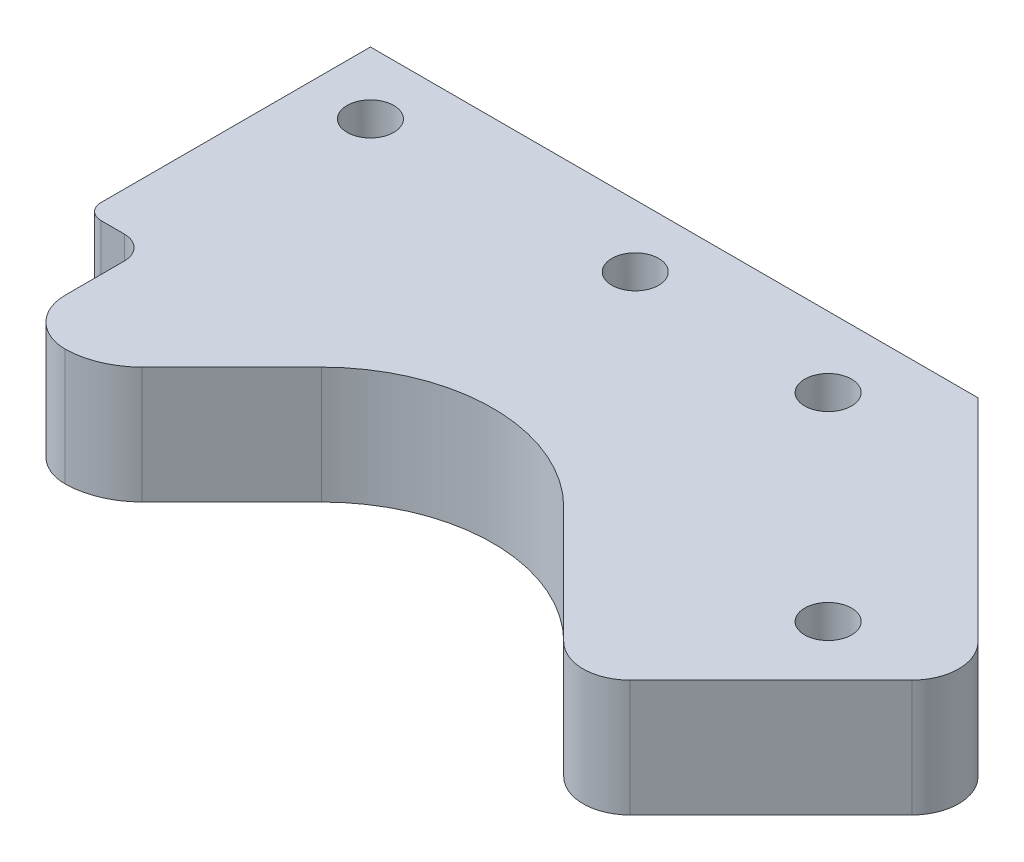
SolidWorks part; units mm, degrees
ref_plane "Front Plane" through (0, 0, 0) normal (0, 0, 1) x (1, 0, 0)
ref_plane "Top Plane" through (0, 0, 0) normal (0, 1, 0) x (1, 0, 0)
ref_plane "Right Plane" through (0, 0, 0) normal (1, 0, 0) x (0, 0, -1)
sketch "Sketch3" plane through (0, 5.4967, 0) normal (0, -1, 0) x (1, 0, 0)
  line L8 (-43.5722, -214.6789) -> (-43.5722, 19.4919) construction
  line L9 (-58.5723, 18.9356) -> (-63.5723, 18.9356)
  line L12 (-35.7941, 11.7137) -> (-26.1725, 21.3353)
  line L13 (-58.5723, 18.9356) -> (-51.3504, 11.7137)
  line L14 (-26.1725, 21.3353) -> (-12.8767, 8.0395)
  line L16 (-28.5722, -7.6561) -> (-12.8767, 8.0395)
  line L17 (-58.5723, -7.6561) -> (-28.5722, -7.6561)
  line L18 (-63.5723, 18.9356) -> (-63.5723, 5.6398)
  line L19 (-43.5722, 19.4919) -> (-32.5722, 19.4919) construction
  line L20 (-58.5723, -7.6561) -> (-63.5723, 5.6398)
  circle A0 centre (-43.5722, 19.4919) radius 11 construction
  arc A2 (-51.3504, 11.7137) -> (-35.7941, 11.7137) centre (-43.5722, 19.4919) ccw
  circle A4 centre (-33.6728, -3.1355) radius 1.5
  circle A5 centre (-20.9448, 9.5924) radius 1.5
extrude "Boss-Extrude1" add sketch "Sketch3" along normal blind 8
sketch "Sketch4" plane through (0, 25.4967, 0) normal (0, 1, 0) x (1, 0, 0)
  line L0 (-67.5734, 21.5545) -> (-67.5734, -11.9295) construction
  line L3 (-65.0723, -10.6398) -> (-67.5734, -10.6398)
  line L4 (-67.5734, 7.6561) -> (-67.5734, -10.6398)
  line L5 (-63.5723, -5.6398) -> (-63.5723, -18.9356)
  line L6 (-63.5723, -12.1398) -> (-63.5723, -18.9356)
  line L10 (-26.1725, -21.3353) -> (-12.8767, -8.0395)
  line L11 (-28.5722, 7.6561) -> (-58.5723, 7.6561)
  line L19 (-28.5722, 7.6561) -> (-67.5734, 7.6561)
  line L21 (-26.1725, -21.3353) -> (-12.8767, -8.0395)
  line L22 (-12.8767, -8.0395) -> (-28.5722, 7.6561)
  line L23 (-12.8767, -8.0395) -> (-28.5722, 7.6561)
  line L26 (-58.5723, 7.6561) -> (-63.5723, -5.6398)
  line L27 (-63.5723, -18.9356) -> (-58.5723, -18.9356)
  line L28 (-63.5723, -18.9356) -> (-58.5723, -18.9356)
  line L29 (-58.5723, -18.9356) -> (-51.3504, -11.7137)
  line L30 (-58.5723, -18.9356) -> (-51.3504, -11.7137)
  line L31 (-35.7941, -11.7137) -> (-26.1725, -21.3353)
  line L32 (-35.7941, -11.7137) -> (-26.1725, -21.3353)
  arc A1 (-35.7941, -11.7137) -> (-51.3504, -11.7137) centre (-43.5722, -19.4919) ccw
  arc A2 (-35.7941, -11.7137) -> (-51.3504, -11.7137) centre (-43.5722, -19.4919) ccw
  arc A3 (-63.5723, -12.1398) -> (-65.0723, -10.6398) centre (-65.0723, -12.1398) ccw
  dimension "D3" = 1.5
  dimension "D1" = 0
extrude "Boss-Extrude2" add sketch "Sketch4" along normal blind 8 separate body
sketch "Sketch9" plane through (0, 25.4967, 0) normal (0, -1, 0) x (1, 0, 0)
  line L0 (-34.7096, -7.6561) -> (-42.7096, 0.3439)
  line L2 (-42.7096, 0.3439) -> (-58.4567, 0.3439)
  line L3 (-34.7096, -7.6561) -> (-58.4567, -7.6561)
  line L4 (-58.4567, -7.6561) -> (-58.4567, 0.3439)
  line L6 (-58.5723, -7.6561) -> (-28.5722, -7.6561) construction
  line L7 (-20.9448, 9.5924) -> (-33.6728, -3.1355) construction
  dimension "D1" = 8
extrude "Boss-Extrude3" add sketch "Sketch9" along normal up to surface (20 mm away) up to face at (-44.3395, 5.4967, 8.6421)
sketch "Sketch10" plane through (0, 0, -7.6561) normal (0, 0, -1) x (-1, 0, 0)
  circle A0 centre (43.5723, 15.4967) radius 5
  circle A1 centre (43.5723, 15.4967) radius 7.5
extrude "Boss-Extrude4" add sketch "Sketch10" along normal blind 10
fillet "Fillet1" radius 3 6 edges at (-26.1725, 29.4967, 21.3353) (-12.8767, 29.4967, 8.0395) (-26.1725, 1.4967, 21.3353) (-12.8767, 1.4967, 8.0395) (-63.5723, 29.4967, 18.9356) (-63.5723, 1.4967, 18.9356)
sketch "Sketch11" plane through (0, 25.4967, 0) normal (0, -1, 0) x (1, 0, 0)
  line L12 (-58.5723, 18.9356) -> (-60.5723, 18.9356)
  line L13 (-63.5723, 15.9356) -> (-63.5723, 12.1398)
  line L15 (-67.5734, -7.6561) -> (-58.4567, -7.6561)
  line L16 (-58.4567, -7.6561) -> (-58.4567, 0.3439)
  line L17 (-58.4567, 0.3439) -> (-42.7096, 0.3439)
  line L18 (-42.7096, 0.3439) -> (-34.7096, -7.6561)
  line L19 (-34.7096, -7.6561) -> (-28.5722, -7.6561)
  line L20 (-28.5722, -7.6561) -> (-14.998, 5.9181)
  line L21 (-14.998, 10.1608) -> (-24.0512, 19.214)
  line L22 (-28.2939, 19.214) -> (-35.7941, 11.7137)
  line L23 (-51.3504, 11.7137) -> (-58.5723, 18.9356)
  line L24 (-58.5723, 18.9356) -> (-60.5723, 18.9356)
  line L25 (-63.5723, 15.9356) -> (-63.5723, 12.1398)
  line L27 (-67.5734, -7.6561) -> (-58.4567, -7.6561)
  line L28 (-58.4567, -7.6561) -> (-58.4567, 0.3439)
  line L29 (-58.4567, 0.3439) -> (-42.7096, 0.3439)
  line L30 (-42.7096, 0.3439) -> (-34.7096, -7.6561)
  line L31 (-34.7096, -7.6561) -> (-28.5722, -7.6561)
  line L32 (-28.5722, -7.6561) -> (-14.998, 5.9181)
  line L33 (-14.998, 10.1608) -> (-24.0512, 19.214)
  line L34 (-28.2939, 19.214) -> (-35.7941, 11.7137)
  line L35 (-51.3504, 11.7137) -> (-58.5723, 18.9356)
  line L39 (-65.0723, 10.6398) -> (-67.5734, 10.6398)
  line L40 (-65.0723, 10.6398) -> (-67.5734, 10.6398)
  line L41 (-67.5734, 10.6398) -> (-67.5734, -7.6561)
  line L42 (-67.5734, 10.6398) -> (-67.5734, -7.6561)
  arc A4 (-60.5723, 18.9356) -> (-63.5723, 15.9356) centre (-60.5723, 15.9356) ccw
  arc A5 (-14.998, 5.9181) -> (-14.998, 10.1608) centre (-17.1193, 8.0395) ccw
  arc A6 (-24.0512, 19.214) -> (-28.2939, 19.214) centre (-26.1725, 17.0926) ccw
  arc A7 (-51.3504, 11.7137) -> (-35.7941, 11.7137) centre (-43.5722, 19.4919) ccw
  arc A8 (-60.5723, 18.9356) -> (-63.5723, 15.9356) centre (-60.5723, 15.9356) ccw
  arc A9 (-14.998, 5.9181) -> (-14.998, 10.1608) centre (-17.1193, 8.0395) ccw
  arc A10 (-24.0512, 19.214) -> (-28.2939, 19.214) centre (-26.1725, 17.0926) ccw
  arc A11 (-51.3504, 11.7137) -> (-35.7941, 11.7137) centre (-43.5722, 19.4919) ccw
  arc A14 (-65.0723, 10.6398) -> (-63.5723, 12.1398) centre (-65.0723, 12.1398) ccw
  arc A15 (-65.0723, 10.6398) -> (-63.5723, 12.1398) centre (-65.0723, 12.1398) ccw
  dimension "D1" = 0
extrude "Cut-Extrude1" cut sketch "Sketch11" against normal blind 0.5
sketch "Sketch12" plane through (0, 5.4967, 0) normal (0, 1, 0) x (1, 0, 0)
  line L0 (-67.5734, -10.6398) -> (-65.0723, -10.6398) construction
  line L1 (-67.5734, 7.6561) -> (-67.5734, -10.6398) construction
  line L3 (-67.5734, -10.6398) -> (-65.0723, -10.6398)
  line L4 (-67.5734, 7.6561) -> (-67.5734, -10.6398)
  line L5 (-65.6492, -5.6398) -> (-67.5734, 7.6561)
  line L12 (-63.5723, -5.6398) -> (-63.5723, -15.9356)
  line L13 (-60.5723, -18.9356) -> (-58.5723, -18.9356)
  line L14 (-58.5723, -18.9356) -> (-51.3504, -11.7137)
  line L15 (-35.7941, -11.7137) -> (-28.2939, -19.214)
  line L16 (-24.0512, -19.214) -> (-14.998, -10.1608)
  line L17 (-14.998, -5.9181) -> (-28.5722, 7.6561)
  line L18 (-28.5722, 7.6561) -> (-34.7096, 7.6561)
  line L19 (-34.7096, 7.6561) -> (-42.7096, -0.3439)
  line L20 (-42.7096, -0.3439) -> (-58.4567, -0.3439)
  line L21 (-58.4567, -0.3439) -> (-58.4567, 7.6561)
  line L22 (-58.4567, 7.6561) -> (-58.5723, 7.6561)
  line L23 (-58.5723, 7.6561) -> (-63.5723, -5.6398)
  line L24 (-63.5723, -12.1398) -> (-63.5723, -15.9356)
  line L25 (-60.5723, -18.9356) -> (-58.5723, -18.9356)
  line L26 (-58.5723, -18.9356) -> (-51.3504, -11.7137)
  line L27 (-35.7941, -11.7137) -> (-28.2939, -19.214)
  line L28 (-24.0512, -19.214) -> (-14.998, -10.1608)
  line L29 (-14.998, -5.9181) -> (-28.5722, 7.6561)
  line L30 (-28.5722, 7.6561) -> (-34.7096, 7.6561)
  line L31 (-34.7096, 7.6561) -> (-42.7096, -0.3439)
  line L32 (-42.7096, -0.3439) -> (-58.4567, -0.3439)
  line L33 (-58.4567, -0.3439) -> (-58.4567, 7.6561)
  line L34 (-58.4567, 7.6561) -> (-58.5723, 7.6561)
  line L35 (-58.5723, 7.6561) -> (-62.8412, -3.6957)
  arc A0 (-65.6492, -5.6398) -> (-62.8412, -3.6957) centre (-65.6492, -2.6398) ccw
  arc A1 (-65.0723, -10.6398) -> (-63.5723, -12.1398) centre (-65.0723, -12.1398) cw
  arc A4 (-63.5723, -15.9356) -> (-60.5723, -18.9356) centre (-60.5723, -15.9356) ccw
  arc A5 (-35.7941, -11.7137) -> (-51.3504, -11.7137) centre (-43.5722, -19.4919) ccw
  arc A6 (-28.2939, -19.214) -> (-24.0512, -19.214) centre (-26.1725, -17.0926) ccw
  arc A7 (-14.998, -10.1608) -> (-14.998, -5.9181) centre (-17.1193, -8.0395) ccw
  arc A8 (-63.5723, -15.9356) -> (-60.5723, -18.9356) centre (-60.5723, -15.9356) ccw
  arc A9 (-35.7941, -11.7137) -> (-51.3504, -11.7137) centre (-43.5722, -19.4919) ccw
  arc A10 (-28.2939, -19.214) -> (-24.0512, -19.214) centre (-26.1725, -17.0926) ccw
  arc A11 (-14.998, -10.1608) -> (-14.998, -5.9181) centre (-17.1193, -8.0395) ccw
  dimension "D1" = 0
extrude "Cut-Extrude2" cut sketch "Sketch12" against normal blind 0.5
chamfer "Chamfer1" distance 3 angle 45 1 edges at (-36.0723, 15.4967, -7.6561)
sketch "Sketch13" plane through (0, 25.9967, 0) normal (0, -1, 0) x (1, 0, 0)
  line L0 (-58.4567, -7.6561) -> (-58.4567, 0.3439) construction
  line L2 (-58.4567, -7.6561) -> (-58.4567, 0.3439)
  line L3 (-67.5734, 0.3439) -> (-67.5734, -7.6561)
  line L4 (-58.4567, 0.3439) -> (-67.5734, 0.3439)
  line L5 (-67.5734, -7.6561) -> (-58.4567, -7.6561) construction
  line L6 (-67.5734, -7.6561) -> (-58.4567, -7.6561)
  line L7 (-67.5734, -21.5548) -> (-67.5734, 11.9292) construction
extrude "Boss-Extrude5" add sketch "Sketch13" along normal up to surface (21 mm away) up to face at (-22.4448, 4.9967, 9.5924)
fillet "Fillet2" radius 15 1 edges at (-63.5723, 1.2467, 5.6398)
fillet "Fillet3" radius 5 2 edges at (-58.5723, 29.7467, 18.9356) (-58.5723, 1.2467, 18.9356)
sketch "Sketch14" plane through (0, -2.5033, 0) normal (0, -1, 0) x (1, 0, 0)
  line L10 (-62.6123, 3.0871) -> (-58.5723, -7.6561) construction
  line L11 (-63.5723, 15.9356) -> (-63.5723, 8.367) construction
  line L12 (-62.6123, 3.0871) -> (-58.5723, -7.6561)
  line L13 (-63.5723, 12.1398) -> (-63.5723, 8.367)
  line L19 (-67.5734, -7.6561) -> (-28.5722, -7.6561)
  line L20 (-28.5722, -7.6561) -> (-12.8767, 8.0395)
  line L21 (-12.8767, 8.0395) -> (-26.1725, 21.3353)
  line L22 (-26.1725, 21.3353) -> (-35.7941, 11.7137)
  line L23 (-51.3504, 11.7137) -> (-58.5723, 18.9356)
  line L24 (-58.5723, 18.9356) -> (-63.5723, 18.9356)
  line L25 (-63.5723, 18.9356) -> (-63.5723, 12.1398)
  line L26 (-65.0723, 10.6398) -> (-67.5734, 10.6398)
  line L27 (-67.5734, 10.6398) -> (-67.5734, -7.6561)
  line L28 (-67.5734, -7.6561) -> (-58.5723, -7.6561)
  line L35 (-65.0723, 10.6398) -> (-67.5734, 10.6398)
  line L36 (-67.5734, 10.6398) -> (-67.5734, -7.6561)
  arc A6 (-63.5723, 8.367) -> (-62.6123, 3.0871) centre (-48.5723, 8.367) ccw construction
  arc A7 (-63.5723, 8.367) -> (-62.6123, 3.0871) centre (-48.5723, 8.367) ccw
  arc A8 (-51.3504, 11.7137) -> (-35.7941, 11.7137) centre (-43.5722, 19.4919) ccw
  arc A9 (-65.0723, 10.6398) -> (-63.5723, 12.1398) centre (-65.0723, 12.1398) ccw
  arc A11 (-65.0723, 10.6398) -> (-63.5723, 12.1398) centre (-65.0723, 12.1398) ccw
  dimension "D1" = 0
extrude "Boss-Extrude6" add sketch "Sketch14" against normal up to surface (7.5 mm away) up to face at (-22.4448, 4.9967, 9.5924)
sketch "Sketch15" plane through (0, -2.5033, 0) normal (0, -1, 0) x (1, 0, 0)
  line L0 (-67.5734, -7.6561) -> (-28.5722, -7.6561) construction
  line L1 (-67.5734, 2.3439) -> (-42.5734, 2.3439)
  line L2 (-67.5734, 2.3439) -> (-67.5734, -7.6561)
  line L3 (-67.5734, -7.6561) -> (-42.5734, -7.6561)
  line L4 (-42.5734, 2.3439) -> (-42.5734, -7.6561)
extrude "Cut-Extrude3" cut sketch "Sketch15" against normal blind 3
sketch "Sketch17" plane through (0, 33.4967, 0) normal (0, 1, 0) x (1, 0, 0)
  line L4 (-67.5734, 7.6561) -> (-67.5734, -2.3439)
  line L5 (-42.5734, 7.6561) -> (-67.5734, 7.6561)
  line L6 (-42.5734, -2.3439) -> (-42.5734, 7.6561)
  line L7 (-67.5734, -2.3439) -> (-42.5734, -2.3439)
  line L8 (-67.5734, 7.6561) -> (-67.5734, -2.3439)
  line L9 (-42.5734, 7.6561) -> (-67.5734, 7.6561)
  line L10 (-42.5734, -2.3439) -> (-42.5734, 7.6561)
  line L11 (-67.5734, -2.3439) -> (-42.5734, -2.3439)
  dimension "D1" = 0
extrude "Cut-Extrude4" cut sketch "Sketch17" against normal blind 3
fillet "Fillet4" radius 3 4 edges at (-42.5734, 31.9967, 2.3439) (-42.5734, 31.9967, -7.6561) (-42.5734, -1.0033, 2.3439) (-42.5734, -1.0033, -7.6561)
sketch "Sketch18" plane through (0, -2.5033, 0) normal (0, -1, 0) x (1, 0, 0)
  circle A0 centre (-46.5734, -3.6561) radius 1.5
  circle A1 centre (-63.5734, -3.6561) radius 1.5
extrude "Cut-Extrude5" cut sketch "Sketch18" against normal up to surface (36 mm away) up to face at (-45.1492, 33.4967, 8.1147)
sketch "Sketch19" plane through (0, 33.4967, 0) normal (0, 1, 0) x (1, 0, 0)
  line L1 (-9.0755, 20.5785) -> (-72.5969, 20.5785)
  line L2 (-9.0755, 20.5785) -> (-9.0755, -23.7161)
  line L3 (-9.0755, -23.7161) -> (-72.5969, -23.7161)
  line L4 (-72.5969, 20.5785) -> (-72.5969, -23.7161)
extrude "Cut-Extrude6" cut sketch "Sketch19" against normal up to surface (28.5 mm away) up to face at (-44.9881, 4.9967, 9.2111)
chamfer "Chamfer2" distance 1.5 angle 45 2 edges at (-32.1728, -2.5033, -3.1355) (-19.4448, -2.5033, 9.5924)
fillet "Fillet5" radius 1 1 edges at (-67.5734, 1.2467, 10.6398)
